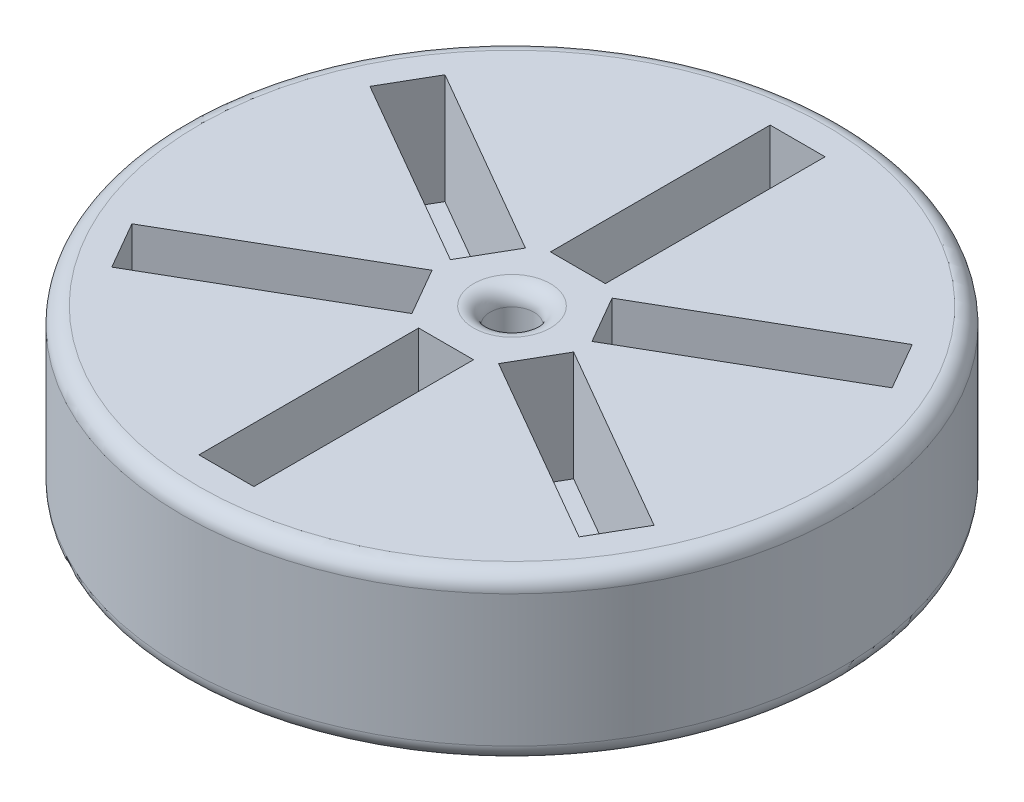
SolidWorks part; units mm, degrees
ref_plane "Front Plane" through (0, 0, 0) normal (0, 0, 1) x (1, 0, 0)
ref_plane "Top Plane" through (0, 0, 0) normal (0, 1, 0) x (1, 0, 0)
ref_plane "Right Plane" through (0, 0, 0) normal (1, 0, 0) x (0, 0, -1)
sketch "Sketch2" plane through (0, 0, 0) normal (0, 1, 0) x (1, 0, 0)
  circle A0 centre (0, 0) radius 30
  dimension "D1" = 60
extrude "Boss-Extrude1" add sketch "Sketch2" along normal blind 15
sketch "Sketch3" plane through (0, 15, 0) normal (0, 1, 0) x (1, 0, 0)
  circle A0 centre (0, 0) radius 2
  dimension "D1" = 4
extrude "Cut-Extrude1" cut sketch "Sketch3" against normal blind 9
fillet "Fillet1" radius 1.5 3 edges at (0, 15, 2) (0, 0, 30) (0, 15, 30)
sketch "Sketch4" plane through (0, 0, 0) normal (0, -1, 0) x (1, 0, 0)
  line L0 (-0.5, 17) -> (-0.5, -27.5)
  line L1 (-0.5, -27.5) -> (0.5, -27.5)
  line L2 (0.5, -27.5) -> (0.5, 17)
  line L3 (0.5, 17) -> (10.5, 17)
  line L4 (10.5, 17) -> (0, 27.5)
  line L5 (0, 27.5) -> (-10.5, 17)
  line L6 (-10.5, 17) -> (-0.5, 17)
  line L7 (0, 27.5) -> (0, -27.5) construction
  line L8 (0, -27.5) -> (0, -28.5) construction
  line L9 (0, 27.5) -> (0, 28.5) construction
  circle A0 centre (0, 0) radius 28.5 construction
  dimension "D2" = 1
  dimension "D1" = 1
  dimension "D3" = 1
  dimension "D4" = 10
extrude "Cut-Extrude2" cut sketch "Sketch4" against normal blind 1
sketch "Sketch5" plane through (0, 15, 0) normal (0, 1, 0) x (1, 0, 0)
  line L0 (0, 6) -> (0, 3.5) construction
  line L1 (-2.5, 26) -> (2.5, 26)
  line L2 (-2.5, 26) -> (-2.5, 6)
  line L3 (-2.5, 6) -> (2.5, 6)
  line L4 (2.5, 26) -> (2.5, 6)
  line L5 (-2.5, 26) -> (2.5, 6) construction
  line L6 (-2.5, 6) -> (2.5, 26) construction
  line L7 (0, 26) -> (0, 28.5) construction
  circle A0 centre (0, 0) radius 3.5 construction
  circle A1 centre (0, 0) radius 28.5 construction
  point P0 (0, 16)
  dimension "D1" = 2.5
  dimension "D2" = 2.5
  dimension "D3" = 5
extrude "Cut-Extrude3" cut sketch "Sketch5" against normal blind 10
pattern_circular "CirPattern1" count 6 over 360 about axis through (0, 6, 0) along (0, 1, 0) of "Cut-Extrude3"
